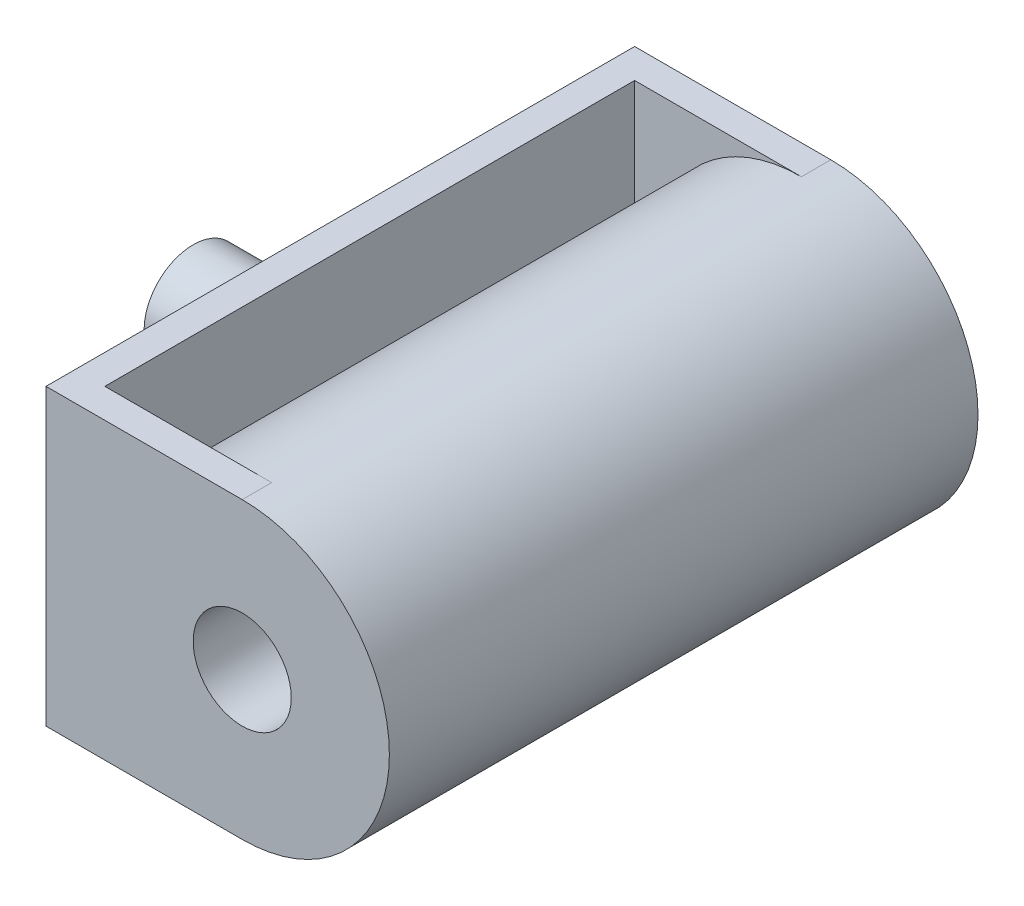
SolidWorks part; units mm, degrees
ref_plane "Front Plane" through (0, 0, 0) normal (0, 0, 1) x (1, 0, 0)
ref_plane "Top Plane" through (0, 0, 0) normal (0, 1, 0) x (1, 0, 0)
ref_plane "Right Plane" through (0, 0, 0) normal (1, 0, 0) x (0, 0, -1)
sketch "Sketch1" plane through (0, 0, 0) normal (0, 0, 1) x (1, 0, 0)
  circle A0 centre (0, 0) radius 15
  dimension "D1" = 30
extrude "Boss-Extrude1" add sketch "Sketch1" along normal blind 60
sketch "Sketch2" plane through (0, 0, 0) normal (0, 1, 0) x (1, 0, 0)
  line L0 (0, 0) -> (-20, 0)
  line L1 (-20, 0) -> (-20, -30)
  line L2 (-17, -30) -> (-20, -30)
  line L5 (-76.3983, -30) -> (22.5078, -30) construction
  line L6 (-15, 0) -> (-15, -60) construction
  line L7 (15, 0) -> (-15, 0) construction
  line L8 (0, 0) -> (0, -3)
  line L9 (-17, -30) -> (-17, -3)
  line L10 (-17, -3) -> (0, -3)
  dimension "D1" = 30
  dimension "D2" = 3
  dimension "D3" = 3
  dimension "D4" = 20
extrude "Boss-Extrude2" add sketch "Sketch2" along normal blind 15 and the other way blind 15
mirror "Mirror1" about plane through (-17, -15, 30) normal (0, 0, 1) of "Boss-Extrude2"
sketch "Sketch3" plane through (-20, 0, 0) normal (-1, 0, 0) x (0, 0, 1)
  line L0 (0, 15) -> (60, 15) construction
  circle A0 centre (30, 0) radius 5
  point P5 (30, 15)
  dimension "D1" = 10
extrude "Boss-Extrude3" add sketch "Sketch3" along normal blind 15
sketch "Sketch4" plane through (0, 0, 60) normal (0, 0, 1) x (1, 0, 0)
  circle A0 centre (0, 0) radius 5
  dimension "D1" = 10
extrude "Cut-Extrude1" cut sketch "Sketch4" against normal blind 146
sketch "Sketch5" plane through (0, 0, 0) normal (0, 1, 0) x (1, 0, 0)
  line L0 (0, -110) -> (0, -30) construction
  line L1 (0, -30) -> (80, -30) construction
  line L2 (-20, 0) -> (-20, -60) construction
  text T0 "Y3" font "Century Gothic" height 20
  text T1 "Z3" font "Century Gothic" height 20
  point P6 (-20, -30)
  dimension "D1" = 80
sketch "Sketch6" plane through (0, 0, 0) normal (1, 0, 0) x (0, 0, -1)
  line L0 (-30, 0) -> (-30, 80) construction
  line L1 (-110, 0) -> (-30, 0) construction
  text T0 "X3" font "Century Gothic" height 20
